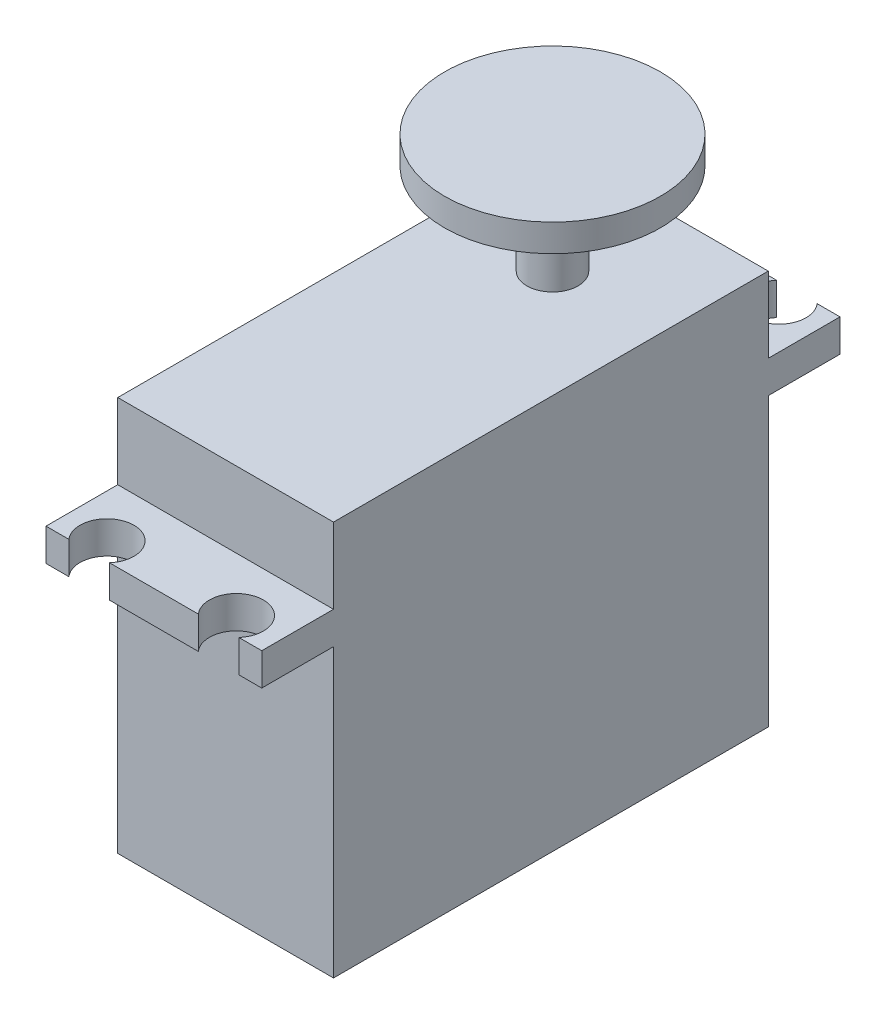
SolidWorks part; units mm, degrees
material "ABS"
ref_plane "Front Plane" through (0, 0, 0) normal (0, 0, 1) x (1, 0, 0)
ref_plane "Top Plane" through (0, 0, 0) normal (0, 1, 0) x (1, 0, 0)
ref_plane "Right Plane" through (0, 0, 0) normal (1, 0, 0) x (0, 0, -1)
sketch "Sketch4" plane through (0, 0, 0) normal (0, 1, 0) x (1, 0, 0)
  circle A0 centre (0, 0) radius 10
  dimension "D1" = 20
extrude "Gear" add sketch "Sketch4" against normal blind 2.54 from offset 47.6 separate body
sketch "Sketch1" plane through (0, 0, 0) normal (0, 1, 0) x (1, 0, 0)
  line L1 (-10, -30.3) -> (10, -30.3)
  line L2 (-10, -30.3) -> (-10, 10)
  line L3 (-10, 10) -> (10, 10)
  line L4 (10, -30.3) -> (10, 10)
  line L5 (-10, -30.3) -> (10, 10) construction
  line L6 (-10, 10) -> (10, -30.3) construction
  circle A0 centre (0, 0) radius 10 construction
  point P4 (0, -10.15)
  dimension "D1" = 20
  dimension "D2" = 40.3
extrude "Body" add sketch "Sketch1" along normal blind 36.6
sketch "Sketch2" plane through (0, 36.6, 0) normal (0, 1, 0) x (1, 0, 0)
  line L0 (0, 10) -> (0, -30.3) construction
  line L1 (10, 10) -> (-10, 10) construction
  line L2 (-10, -30.3) -> (10, -30.3) construction
  circle A0 centre (0, 0) radius 2.3813
  circle A1 centre (0, 0) radius 10 construction
  dimension "D2" = 4.7625
extrude "Axle" add sketch "Sketch2" along normal up to next
sketch "Sketch3" plane through (0, 0, 0) normal (0, 1, 0) x (1, 0, 0)
  line L0 (10, -30.3) -> (10, 10) construction
  line L1 (-10, 10) -> (10, 10)
  line L2 (-10, 10) -> (-10, 16.65)
  line L3 (-10, 16.65) -> (10, 16.65)
  line L4 (10, 10) -> (10, 16.65)
  line L5 (-10, 10) -> (10, 16.65) construction
  line L6 (-10, 16.65) -> (10, 10) construction
  line L7 (-10, 15) -> (10, 15) construction
  line L8 (-10, -30.3) -> (10, -30.3) construction
  line L9 (-10, -30.3) -> (-10, -36.95) construction
  line L10 (-10, -36.95) -> (10, -36.95) construction
  line L11 (10, -30.3) -> (10, -36.95) construction
  line L12 (-10, -30.3) -> (10, -36.95) construction
  line L13 (-10, -36.95) -> (10, -30.3) construction
  circle A0 centre (-6, 15) radius 2.5
  circle A1 centre (6, 15) radius 2.5
  point P4 (0, 13.325)
  point P12 (0, -33.625)
  dimension "D2" = 5
  dimension "D1" = 53.6
  dimension "D3" = 4
  dimension "D4" = 4
  dimension "D5" = 5
extrude "Wings" add sketch "Sketch3" along normal blind 3 from offset 26.6 contours A1 L3 A0 L2 L1 L4 region at (0, 0, -12.8204)
ref_plane "Plane1" through (0, 0, 10.15) normal (0, 0, 1) x (1, 0, 0)
mirror "Mirror1" about plane through (0, 0, 10.15) normal (0, 0, 1) of "Wings"
